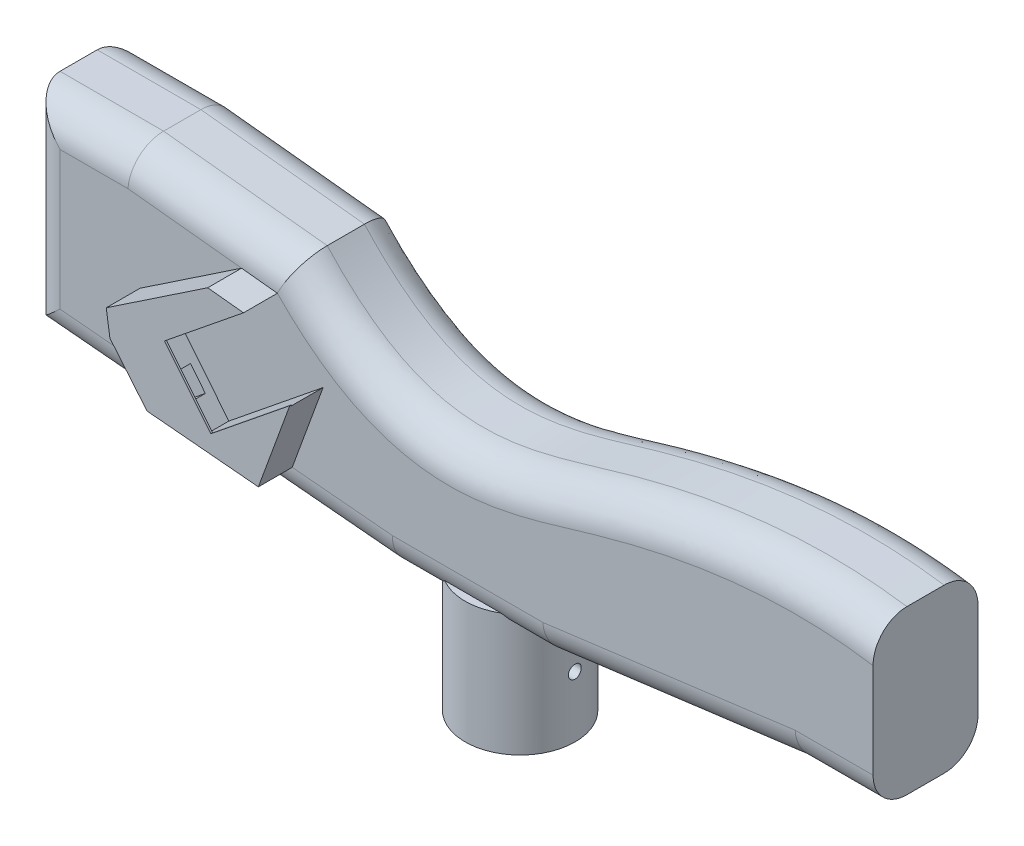
SolidWorks part; units mm, degrees
ref_plane "前基準面" through (0, 0, 0) normal (0, 0, 1) x (1, 0, 0)
ref_plane "上基準面" through (0, 0, 0) normal (0, 1, 0) x (1, 0, 0)
ref_plane "右基準面" through (0, 0, 0) normal (1, 0, 0) x (0, 0, -1)
sketch "草圖1" plane through (0, 0, 0) normal (0, 0, 1) x (1, 0, 0)
  line L0 (0, 0) -> (0, 60)
  line L1 (0, 60) -> (30.6281, 60)
  line L2 (30.6281, 60) -> (78.9616, 54.8725)
  line L3 (280.2175, 40) -> (280.2175, 0)
  line L4 (280.2175, 0) -> (227.8434, 0)
  line L5 (153.3118, -9.6901) -> (107.7898, -9.6901)
  spline S0 degree 3 poles (78.9616, 54.8725) (110.7562, 20.0434) (172.1725, 47.6811) (243.4018, 55.0032) (280.2175, 40) knots 0 0 0 0 0.434694 1 1 1 1
  spline S1 degree 1 poles (227.8434, 0) (153.3118, -9.6901) knots 0 0 1 1
  spline S2 degree 1 poles (107.7898, -9.6901) (0, 0) knots 0 0 1 1
  dimension "D1" = 40
  dimension "D2" = 60
extrude "填料-伸長1" add sketch "草圖1" along normal blind 31
fillet "圓角3" radius 10 9 edges at (0, 30, 31) (15.3141, 60, 31) (54.7949, 57.4363, 31) (280.2175, 20, 31) (254.0304, 0, 31) (130.5508, -9.6901, 31)
fillet "圓角4" radius 10 9 edges at (130.5508, -9.6901, 0) (254.0304, 0, 0) (280.2175, 20, 0) (54.7949, 57.4363, 0) (15.3141, 60, 0) (0, 30, 0)
ref_plane "平面1" through (0, -11, 0) normal (0, 1, 0) x (1, 0, 0)
sketch "草圖4" plane through (0, -11, 0) normal (0, 1, 0) x (1, 0, 0)
  line L0 (-1000, -15.5) -> (49000, -15.5) construction
  line L1 (0, -21) -> (0, -10) construction
  line L2 (130.4514, -1000) -> (130.4514, 49000) construction
  line L3 (152.6645, 0) -> (108.2383, 0) construction
  circle A0 centre (130.4455, -15.5) radius 6.25
  point P5 (0, -15.5)
  point P10 (130.4514, 0)
  dimension "D1" = 12.5
extrude "伸長-薄件1" add sketch "草圖4" against normal blind 30 and the other way blind 6 thin thin type one direction wall 10
ref_plane "平面2" through (0, 0, 0) normal (1, 0, 0) x (0, 0, -1)
sketch "草圖9" plane through (0, 0, 0) normal (1, 0, 0) x (0, 0, -1)
  line L0 (-15.5, -940) -> (-15.5, 49060) construction
  line L1 (-21, 60) -> (-10, 60) construction
  line L2 (-1000, 29.5707) -> (49000, 29.5707) construction
  line L3 (0, 9.1413) -> (0, 50) construction
  line L5 (-2.5, 39.1457) -> (-28.5, 39.1457)
  line L6 (-2.5, 39.1457) -> (-2.5, 19.9957)
  line L7 (-2.5, 19.9957) -> (-28.5, 19.9957)
  line L8 (-28.5, 39.1457) -> (-28.5, 19.9957)
  line L9 (-2.5, 39.1457) -> (-28.5, 19.9957) construction
  line L10 (-2.5, 19.9957) -> (-28.5, 39.1457) construction
  point P5 (-15.5, 60)
  point P6 (-15.5, 29.5707)
  point P10 (0, 29.5707)
  dimension "D1" = 26
  dimension "D2" = 19.15
extrude "除料-伸長1" cut sketch "草圖9" along normal blind 70
sketch "草圖10" plane through (0, -11, 0) normal (0, 1, 0) x (1, 0, 0)
  line L0 (-1000.0198, -14.528) -> (48999.9802, -14.528) construction
  line L3 (20.3548, -5.528) -> (36.3548, -5.528)
  line L4 (20.3548, -5.528) -> (20.3548, -23.528)
  line L5 (20.3548, -23.528) -> (36.3548, -23.528)
  line L6 (36.3548, -5.528) -> (36.3548, -23.528)
  line L7 (20.3548, -5.528) -> (36.3548, -23.528) construction
  line L8 (20.3548, -23.528) -> (36.3548, -5.528) construction
  point P1 (28.3548, -14.528)
  dimension "D1" = 18
  dimension "D2" = 18
  dimension "D3" = 16
extrude "除料-伸長3" cut sketch "草圖10" along normal blind 37
sketch "草圖11" plane through (70, 0, 0) normal (-1, 0, 0) x (0, 0, 1)
  line L0 (10, 39.1457) -> (21, 39.1457) construction
  line L1 (4.5, 37.1457) -> (26.5, 37.1457)
  line L2 (4.5, 37.1457) -> (4.5, 21.9957)
  line L3 (4.5, 21.9957) -> (26.5, 21.9957)
  line L4 (26.5, 37.1457) -> (26.5, 21.9957)
  line L5 (4.5, 37.1457) -> (26.5, 21.9957) construction
  line L6 (4.5, 21.9957) -> (26.5, 37.1457) construction
  line L7 (28.5, 19.9957) -> (2.5, 19.9957) construction
  line L8 (2.5, 19.9957) -> (2.5, 39.1457) construction
  line L9 (28.5, 39.1457) -> (28.5, 19.9957) construction
  point P0 (15.5, 29.5707)
  dimension "D1" = 2
  dimension "D2" = 2
  dimension "D3" = 2
  dimension "D4" = 2
extrude "除料-伸長4" cut sketch "草圖11" against normal blind 22
sketch "草圖12" plane through (0, 0, 31) normal (0, 0, 1) x (1, 0, 0)
  line L1 (280.2175, 0) -> (250.2175, 0)
  line L2 (280.2175, 0) -> (280.2175, 58.699)
  line L3 (280.2175, 58.699) -> (250.2175, 58.699)
  line L4 (250.2175, 0) -> (250.2175, 58.699)
  dimension "D1" = 30
extrude "除料-伸長5" cut sketch "草圖12" against normal blind 54
sketch "草圖13" plane through (0, 0, 0) normal (1, 0, 0) x (0, 0, -1)
  line L0 (-994.25, -23) -> (49005.75, -23) construction
  line L1 (0.75, -41) -> (0.75, -5) construction
  line L2 (-15.5, -1041) -> (-15.5, 48959) construction
  line L3 (-31.75, -41) -> (0.75, -41) construction
  circle A0 centre (-15.5, -23) radius 1.91
  point P5 (0.75, -23)
  point P10 (-15.5, -41)
  dimension "D1" = 3.82
extrude "除料-伸長6" cut sketch "草圖13" along normal blind 184
sketch "草圖15" plane through (0, 0, 31) normal (0, 0, 1) x (1, 0, 0)
  line L0 (30.0992, 50) -> (74.2225, 45.3192)
  line L1 (74.2225, 45.3192) -> (87.8973, 28.3987)
  line L2 (87.8973, 28.3987) -> (78.608, 2.9736)
  line L3 (10, 9.1413) -> (108.2383, 0.3099) construction
  line L4 (78.608, 2.9736) -> (36.6069, 6.7494)
  line L5 (36.6069, 6.7494) -> (30.0992, 50)
extrude "填料-伸長2" add sketch "草圖15" along normal blind 10
sketch "草圖20" plane through (0, 0, 41) normal (0, 0, 1) x (1, 0, 0)
  line L0 (63.6448, 46.4413) -> (33.6621, 26.3206)
  line L1 (74.2225, 45.3192) -> (30.0992, 50) construction
  line L2 (30.0992, 50) -> (36.6069, 6.7494) construction
  line L3 (33.6621, 26.3206) -> (30.0992, 50)
  line L4 (30.0992, 50) -> (63.6448, 46.4413)
extrude "除料-伸長9" cut sketch "草圖20" against normal blind 10
sketch "草圖23" plane through (0, 0, 41) normal (0, 0, 1) x (1, 0, 0)
  line L0 (36.6069, 6.7494) -> (45.7263, 5.9296)
  line L1 (36.6069, 6.7494) -> (78.608, 2.9736) construction
  line L2 (45.7263, 5.9296) -> (34.753, 19.0707)
  line L3 (33.6621, 26.3206) -> (36.6069, 6.7494) construction
  line L4 (34.753, 19.0707) -> (36.6069, 6.7494)
extrude "除料-伸長16" cut sketch "草圖23" against normal blind 10 contours L2 L4 L0
sketch "草圖26" plane through (67.0528, 54.1907, 0) normal (0.7778, 0.6286, 0) x (0, 0, -1)
  line L0 (-41, -33.162) -> (-41, -11.4065) construction
  line L1 (-31, -11.4065) -> (-40.5, -11.4065)
  line L2 (-31, -11.4065) -> (-31, -33.4065)
  line L3 (-31, -33.4065) -> (-40.5, -33.4065)
  line L4 (-40.5, -11.4065) -> (-40.5, -33.4065)
  dimension "D1" = 22
  dimension "D2" = 0.5
extrude "除料-伸長17" cut sketch "草圖26" against normal blind 36.2
sketch "草圖27" plane through (38.898, 31.4366, 0) normal (0.7778, 0.6286, 0) x (0, 0, -1)
  line L0 (-35.75, -1011.4065) -> (-35.75, 48988.5935) construction
  line L1 (-31, -11.4065) -> (-40.5, -11.4065) construction
  line L2 (-1040.5, -22.4065) -> (48959.5, -22.4065) construction
  line L3 (-40.5, -11.4065) -> (-40.5, -33.4065) construction
  line L5 (-38.26, -18.9065) -> (-33.24, -18.9065)
  line L6 (-38.26, -18.9065) -> (-38.26, -25.9065)
  line L7 (-38.26, -25.9065) -> (-33.24, -25.9065)
  line L8 (-33.24, -18.9065) -> (-33.24, -25.9065)
  line L9 (-38.26, -18.9065) -> (-33.24, -25.9065) construction
  line L10 (-38.26, -25.9065) -> (-33.24, -18.9065) construction
  point P5 (-35.75, -11.4065)
  point P6 (-35.75, -22.4065)
  point P10 (-40.5, -22.4065)
  dimension "D1" = 7
  dimension "D2" = 5.02
extrude "除料-伸長18" cut sketch "草圖27" against normal blind 36.2
sketch "草圖28" plane through (0, 0, 40.5) normal (0, 0, -1) x (-1, 0, 0)
  line L0 (-76.9987, 41.8841) -> (-48.9307, 19.023) construction
  line L1 (-87.8973, 28.3987) -> (-74.2225, 45.3192) construction
  dimension "D1" = 36.2
sketch "草圖29" plane through (67.0528, 54.1907, 0) normal (0.7778, 0.6286, 0) x (0, 0, -1)
  line L0 (-41, -11.4065) -> (-40.5, -11.4065)
  line L1 (-40.5, -11.4065) -> (-40.5, -33.162)
  line L2 (-40.5, -33.162) -> (-41, -33.162)
  line L3 (-41, -33.162) -> (-41, -11.4065)
extrude "除料-伸長19" cut sketch "草圖29" against normal blind 30
